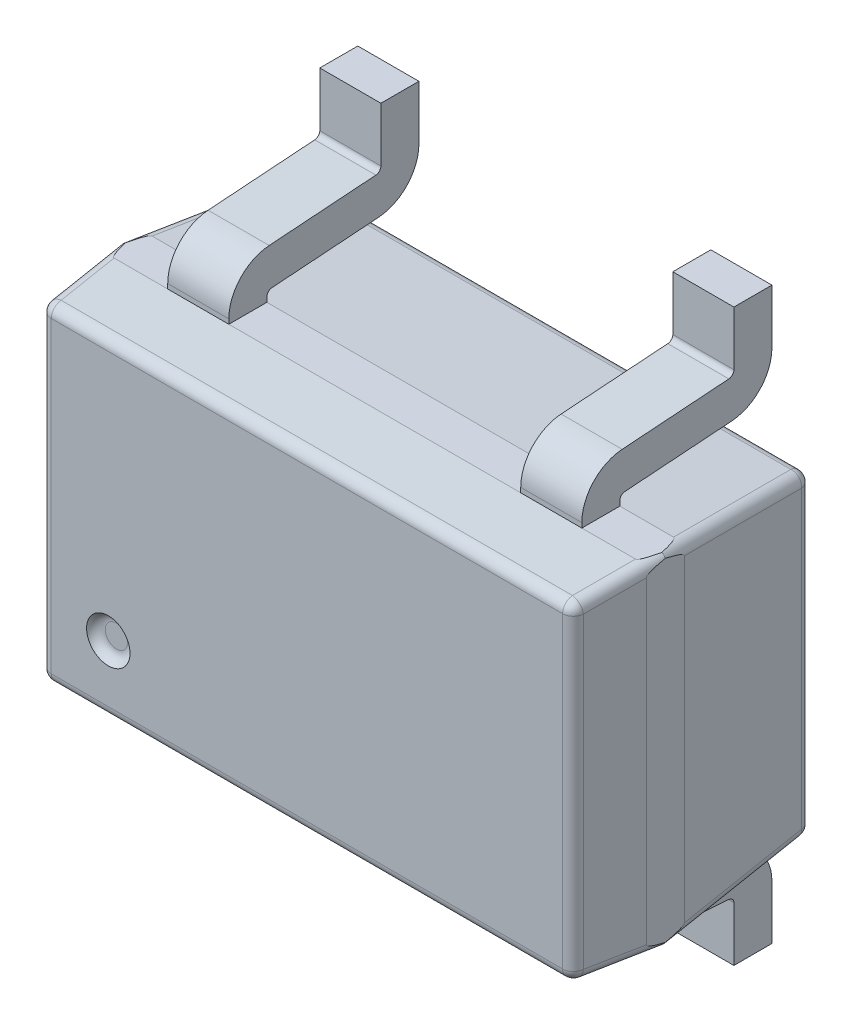
SolidWorks part; units mm, degrees
ref_plane "Alzado" through (0, 0, 0) normal (0, 0, 1) x (1, 0, 0)
ref_plane "Planta" through (0, 0, 0) normal (0, 1, 0) x (1, 0, 0)
ref_plane "Vista lateral" through (0, 0, 0) normal (1, 0, 0) x (0, 0, -1)
sketch "Croquis1" plane through (0, 0, 0) normal (0, 0, 1) x (1, 0, 0)
  line L1 (-1, -0.625) -> (1, -0.625)
  line L2 (-1, -0.625) -> (-1, 0.625)
  line L3 (-1, 0.625) -> (1, 0.625)
  line L4 (1, -0.625) -> (1, 0.625)
  line L5 (-1, -0.625) -> (1, 0.625) construction
  line L6 (-1, 0.625) -> (1, -0.625) construction
  point P0 (0, 0)
  dimension "D1" = 1.25
  dimension "D2" = 2
extrude "Saliente-Extruir1" add sketch "Croquis1" along normal blind 0.51 from offset 0.05
chamfer "Chaflán1" distance 0.51 angle 5 4 edges at (0, 0.625, 0.05) (0, -0.625, 0.05) (-1, 0, 0.05) (1, 0, 0.05) first distance on face at (0, 0.625, 0.305) first distance on face at (0, -0.625, 0.305) first distance on face at (-1, 0, 0.305) first distance on face at (1, 0, 0.305)
sketch "Croquis2" plane through (0, 0, 0.56) normal (0, 0, 1) x (1, 0, 0)
  line L1 (-1, -0.625) -> (1, -0.625)
  line L2 (-1, -0.625) -> (-1, 0.625)
  line L3 (-1, 0.625) -> (1, 0.625)
  line L4 (1, -0.625) -> (1, 0.625)
  line L5 (-1, -0.625) -> (1, 0.625) construction
  line L6 (-1, 0.625) -> (1, -0.625) construction
  point P0 (0, 0)
extrude "Saliente-Extruir2" add sketch "Croquis2" along normal blind 0.39
chamfer "Chaflán2" distance 0.25 angle 5 4 edges at (-1, 0, 0.95) (0, -0.625, 0.95) (1, 0, 0.95) (0, 0.625, 0.95) first distance on face at (-1, 0, 0.755) first distance on face at (0, -0.625, 0.755) first distance on face at (1, 0, 0.755) first distance on face at (0, 0.625, 0.755)
fillet "Redondeo1" radius 0.04 16 edges at (0, 0.5804, 0.05) (-0.9554, 0, 0.05) (0, -0.5804, 0.05) (0.9554, 0, 0.05) (0.9781, 0, 0.95) (0, -0.6031, 0.95) (-0.9781, 0, 0.95) (0, 0.6031, 0.95) (0.9777, -0.6027, 0.305) (0.9891, -0.6141, 0.825) (0.9891, 0.6141, 0.825) (0.9777, 0.6027, 0.305) (-0.9777, 0.6027, 0.305) (-0.9891, 0.6141, 0.825) (-0.9777, -0.6027, 0.305) (-0.9891, -0.6141, 0.825)
sketch "Croquis4" plane through (0, 0, 0) normal (1, 0, 0) x (0, 0, -1)
  line L0 (-0.56, -0.625) -> (-0.56, -0.6424)
  line L1 (-0.5414, -0.6623) -> (-0.1486, -0.6904)
  line L2 (0, -0.85) -> (0, -1.05)
  line L3 (0, 0) -> (-0.7594, 0) construction
  arc A0 (-0.1486, -0.6904) -> (0, -0.85) centre (-0.16, -0.85) cw
  arc A1 (-0.56, -0.6424) -> (-0.5414, -0.6623) centre (-0.54, -0.6424) ccw
  point P9 (0, -0.701)
  point P12 (-0.56, -0.661)
  dimension "D5" = 0.2
  dimension "D1" = 0.425
  dimension "D2" = 0.16
  dimension "D6" = 0.02
  dimension "D3" = 0.076
  dimension "D4" = 0.04
extrude "Extruir-Lámina1" add sketch "Croquis4" along normal mid plane 0.225 thin thin type one direction wall 0.14
pattern_linear "MatrizL2" count 2 spacing 0.65 along (1, 0, 0) count 2 spacing 0.65 along (-1, 0, 0) of "Extruir-Lámina1"
mirror "Simetría2" about plane through (0, 0, 0) normal (0, 1, 0) of "MatrizL2"
sketch "Croquis7" plane through (0.1125, 0, 0) normal (1, 0, 0) x (0, 0, -1)
  line L1 (-0.7, 0.625) -> (0, 0.625)
  line L2 (-0.7, 0.625) -> (-0.7, 1.05)
  line L3 (-0.7, 1.05) -> (0, 1.05)
  line L4 (0, 0.625) -> (0, 1.05)
extrude "Cortar-Extruir1" cut sketch "Croquis7" against normal blind 0.225
sketch "Croquis8" plane through (0, 0, 0.95) normal (0, 0, 1) x (1, 0, 0)
  line L0 (-0.9813, -0.5665) -> (-0.9813, 0.5665) construction
  line L1 (0.9415, -0.6063) -> (-0.9415, -0.6063) construction
  circle A0 centre (-0.7313, -0.3563) radius 0.08
  dimension "D1" = 0.25
  dimension "D2" = 0.25
extrude "Cortar-Extruir3" cut sketch "Croquis8" against normal blind 0.03
fillet "Redondeo2" radius 0.04 1 edges at (-0.6513, -0.3563, 0.92)
